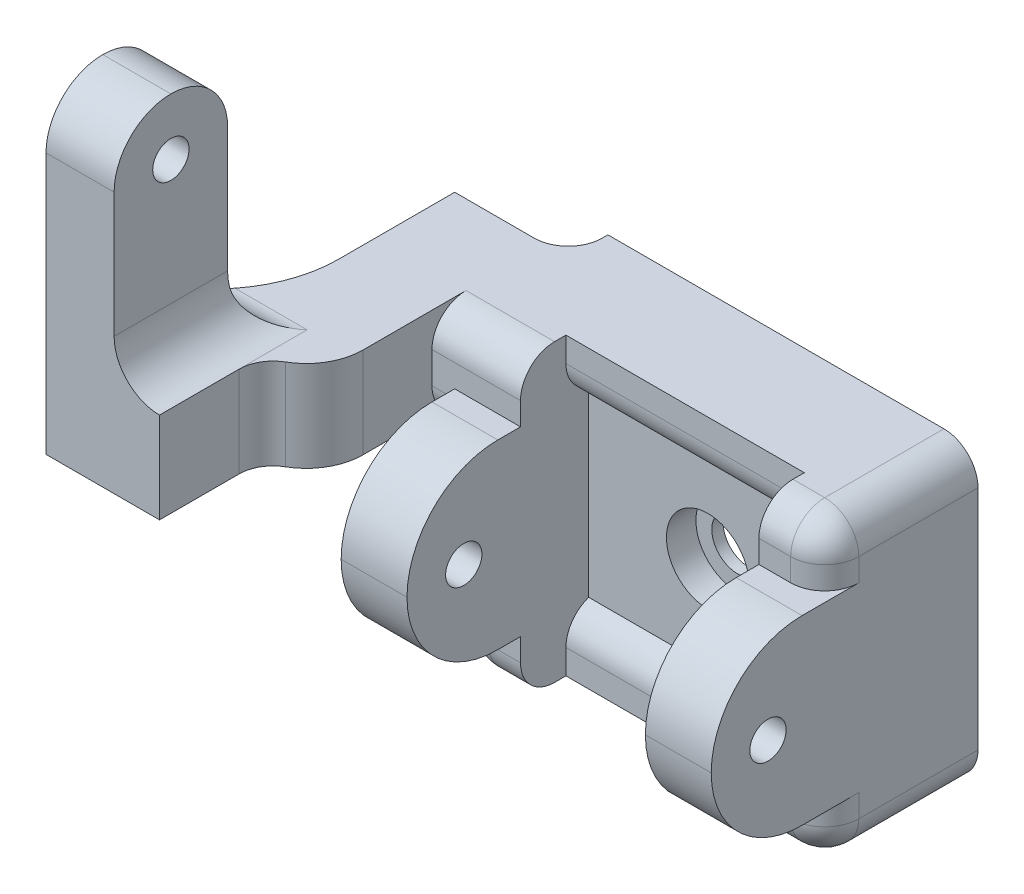
SolidWorks part; units mm, degrees
ref_plane "Front" through (0, 0, 0) normal (0, 0, 1) x (1, 0, 0)
ref_plane "Top" through (0, 0, 0) normal (0, 1, 0) x (1, 0, 0)
ref_plane "Right" through (0, 0, 0) normal (1, 0, 0) x (0, 0, -1)
sketch "Sketch1" plane through (0, 0, 0) normal (0, 0, 1) x (1, 0, 0)
  line L1 (0, 0) -> (-32.6, 0)
  line L2 (0, 0) -> (0, 26)
  line L3 (0, 26) -> (-32.6, 26)
  line L4 (-32.6, 0) -> (-32.6, 26)
  dimension "D1" = 32.6
  dimension "D2" = 26
extrude "Boss-Extrude1" add sketch "Sketch1" along normal blind 4
sketch "Sketch2" plane through (0, 0, 4) normal (0, 0, 1) x (1, 0, 0)
  line L0 (0, 26) -> (-32.6, 26) construction
  line L1 (0, 0) -> (0, 26) construction
  circle A0 centre (-16.3, 13) radius 3.65
  dimension "D1" = 7.3
  dimension "D2" = 13
  dimension "D3" = 16.3
extrude "Cut-Extrude1" cut sketch "Sketch2" against normal blind 2.6
sketch "Sketch3" plane through (0, 0, 1.4) normal (0, 0, 1) x (1, 0, 0)
  circle A0 centre (-16.3, 13) radius 2.25
  dimension "D1" = 4.5
extrude "Cut-Extrude2" cut sketch "Sketch3" against normal through all
sketch "Sketch4" plane through (0, 0, 4) normal (0, 0, 1) x (1, 0, 0)
  line L0 (-32.6, 0) -> (0, 0) construction
  line L1 (0, 26) -> (-5.8, 26)
  line L2 (0, 26) -> (0, 0)
  line L3 (0, 0) -> (-5.8, 0)
  line L4 (-5.8, 26) -> (-5.8, 0)
  line L6 (-32.6, 26) -> (-26.8, 26)
  line L7 (-32.6, 26) -> (-32.6, 0)
  line L8 (-32.6, 0) -> (-26.8, 0)
  line L9 (-26.8, 26) -> (-26.8, 0)
  dimension "D1" = 5.8
  dimension "D2" = 5.8
extrude "Boss-Extrude2" add sketch "Sketch4" along normal blind 16
sketch "Sketch5" plane through (0, 0, 0) normal (1, 0, 0) x (0, 0, -1)
  line L0 (-20, 0) -> (-20, 26) construction
  line L1 (-20, 0) -> (0, 0) construction
  circle A0 centre (-15, 13) radius 1.6
  dimension "D1" = 3.2
  dimension "D2" = 5
  dimension "D3" = 13
extrude "Cut-Extrude3" cut sketch "Sketch5" against normal through all
sketch "Sketch6" plane through (0, 0, 4) normal (0, 0, 1) x (1, 0, 0)
  line L1 (-26.8, 26) -> (-5.8, 26)
  line L2 (-26.8, 26) -> (-26.8, 21)
  line L3 (-26.8, 21) -> (-5.8, 21)
  line L4 (-5.8, 26) -> (-5.8, 21)
  line L5 (-26.8, 0) -> (-5.8, 0)
  line L6 (-26.8, 0) -> (-26.8, 5)
  line L7 (-26.8, 5) -> (-5.8, 5)
  line L8 (-5.8, 0) -> (-5.8, 5)
  dimension "D1" = 5
  dimension "D2" = 5
extrude "Boss-Extrude3" add sketch "Sketch6" along normal blind 2
sketch "Sketch7" plane through (-32.6, 0, 0) normal (-1, 0, 0) x (0, 0, 1)
  line L1 (20, 26) -> (10, 26)
  line L2 (20, 26) -> (20, 21)
  line L3 (20, 21) -> (10, 21)
  line L4 (10, 26) -> (10, 21)
  line L5 (20, 0) -> (10, 0)
  line L6 (20, 0) -> (20, 5)
  line L7 (20, 5) -> (10, 5)
  line L8 (10, 0) -> (10, 5)
  dimension "D1" = 10
  dimension "D2" = 10
  dimension "D3" = 5
  dimension "D4" = 5
extrude "Cut-Extrude4" cut sketch "Sketch7" against normal through all
fillet "Fillet1" radius 8 4 edges at (-2.9, 5, 20) (-2.9, 21, 20) (-29.7, 5, 20) (-29.7, 21, 20)
sketch "Sketch12" plane through (-32.6, 0, 0) normal (-1, 0, 0) x (0, 0, 1)
  line L0 (0, 26) -> (0, 0) construction
  line L1 (10, 26) -> (0, 26)
  line L2 (10, 26) -> (10, 18)
  line L3 (10, 18) -> (0, 18)
  line L4 (0, 26) -> (0, 18)
  dimension "D1" = 8
extrude "Boss-Extrude8" add sketch "Sketch12" along normal blind 10
sketch "Sketch13" plane through (0, 0, 10) normal (0, 0, 1) x (1, 0, 0)
  line L0 (-26.8, 26) -> (-42.6, 26) construction
  line L1 (-42.6, 18) -> (-34.6, 18)
  line L2 (-42.6, 18) -> (-42.6, 26)
  line L3 (-42.6, 26) -> (-34.6, 26)
  line L4 (-34.6, 18) -> (-34.6, 26)
  dimension "D1" = 8
extrude "Boss-Extrude9" add sketch "Sketch13" along normal blind 10
fillet "Fillet2" radius 3 4 edges at (-30.7, 26, 10) (-2.9, 26, 10) (-2.9, 0, 10) (-29.7, 0, 10)
sketch "Sketch14" plane through (0, 0, 20) normal (0, 0, 1) x (1, 0, 0)
  line L0 (-42.6, 18) -> (-34.6, 18) construction
  line L1 (-38.6, 18) -> (-48.6, 18)
  line L2 (-38.6, 18) -> (-38.6, 26)
  line L3 (-38.6, 26) -> (-48.6, 26)
  line L4 (-48.6, 18) -> (-48.6, 26)
  dimension "D1" = 8
  dimension "D2" = 10
extrude "Boss-Extrude10" add sketch "Sketch14" along normal blind 10
sketch "Sketch15" plane through (0, 26, 0) normal (0, 1, 0) x (1, 0, 0)
  line L1 (-48.6, -30) -> (-42.6, -30)
  line L2 (-48.6, -30) -> (-48.6, -20)
  line L3 (-48.6, -20) -> (-42.6, -20)
  line L4 (-42.6, -30) -> (-42.6, -20)
  dimension "D1" = 10
  dimension "D2" = 6
extrude "Boss-Extrude11" add sketch "Sketch15" along normal blind 20
fillet "Fillet10" radius 11 1 edges at (-42.6, 22, 20)
fillet "Fillet11" radius 3 1 edges at (-38.6, 22, 20)
fillet "Fillet12" radius 5 1 edges at (-34.6, 22, 20)
fillet "Fillet14" radius 4 1 edges at (-42.6, 26, 25)
fillet "Fillet15" radius 3 1 edges at (-43.6, 26, 20)
sketch "Sketch16" plane through (0, 0, 0) normal (0, 0, -1) x (-1, 0, 0)
  line L0 (42.6, 18) -> (32.6, 18)
  line L1 (32.6, 18) -> (32.6, 9)
  line L2 (32.6, 18) -> (32.6, 0) construction
  line L3 (32.6, 9) -> (42.6, 18)
  dimension "D1" = 9
extrude "Boss-Extrude12" add sketch "Sketch16" against normal blind 9
fillet "Fillet17" radius 3 1 edges at (-32.6, 9, 4.5)
fillet "Fillet18" radius 3 1 edges at (-33.6, 18, 10)
sketch "Sketch17" plane through (-48.6, 0, 0) normal (-1, 0, 0) x (0, 0, 1)
  line L0 (30, 46) -> (30, 18) construction
  line L1 (20, 46) -> (30, 46) construction
  circle A0 centre (25, 41) radius 1.6
  dimension "D1" = 3.2
  dimension "D2" = 5
  dimension "D3" = 5
extrude "Cut-Extrude5" cut sketch "Sketch17" against normal through all
fillet "Fillet19" radius 5 2 edges at (-45.6, 46, 20) (-45.6, 46, 30)
fillet "Fillet21" radius 3 2 edges at (-16.3, 21, 6) (-16.3, 5, 6)
sketch "Sketch18" plane through (0, 0, 0) normal (0, 0, -1) x (-1, 0, 0)
  line L0 (0, 0) -> (0, 26) construction
  line L1 (32.6, 0) -> (0, 0)
  line L2 (32.6, 0) -> (32.6, 26)
  line L3 (32.6, 26) -> (0, 26)
  line L4 (0, 0) -> (0, 26)
extrude "Boss-Extrude13" add sketch "Sketch18" along normal blind 3.5
sketch "Sketch19" plane through (0, 0, -3.5) normal (0, 0, -1) x (-1, 0, 0)
  circle A0 centre (16.3, 13) radius 9.15
  dimension "D1" = 18.3
extrude "Cut-Extrude6" cut sketch "Sketch19" against normal blind 3.9
fillet "Fillet22" radius 3 9 edges at (0, 22, 10) (0, 25.1213, 9.1213) (0, 4, 10) (0, 0.8787, 9.1213) (-32.6, 4, 10) (-32.6, 0.8787, 9.1213) (0, 26, 1.75) (0, 0, 1.75) (-32.6, 0, 1.75)
fillet "Fillet23" radius 3 1 edges at (-32.6, 16.832, 0)
sketch "Sketch20" plane through (0, 0, 0) normal (0, -1, 0) x (-1, 0, 0)
  line L0 (3, 3.5) -> (29.6, 3.5) construction
  line L1 (3, 3.5) -> (3, -7) construction
  circle A0 centre (16.3, 0.5) radius 1
  dimension "D3" = 2
  dimension "D1" = 3
  dimension "D2" = 13.3
extrude "Cut-Extrude7" cut sketch "Sketch20" against normal blind 4
